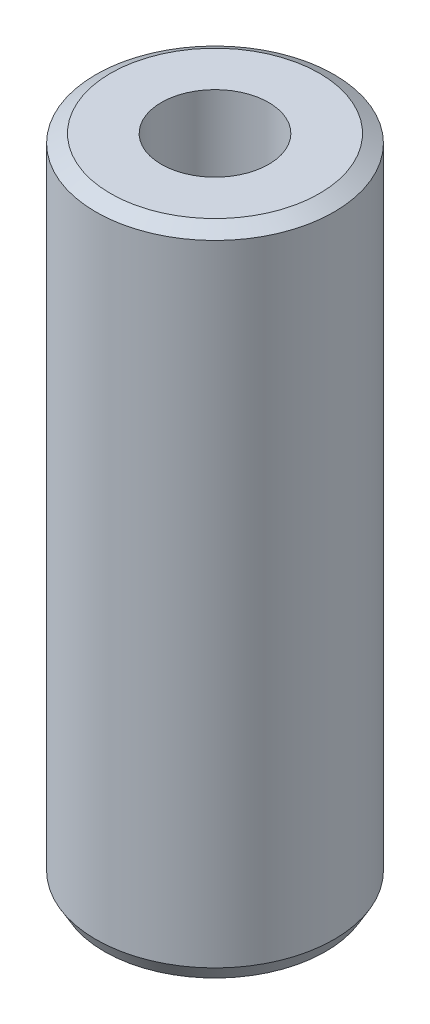
SolidWorks part; units mm, degrees
ref_plane "Front Plane" through (0, 0, 0) normal (0, 0, 1) x (1, 0, 0)
ref_plane "Top Plane" through (0, 0, 0) normal (0, 1, 0) x (1, 0, 0)
ref_plane "Right Plane" through (0, 0, 0) normal (1, 0, 0) x (0, 0, -1)
sketch "Sketch1" plane through (0, 0, 0) normal (0, 1, 0) x (1, 0, 0)
  circle A0 centre (0, 0) radius 47.5
  dimension "SHAFT_OD" = 95
extrude "Boss-Extrude1" add sketch "Sketch1" along normal blind 260.5429
sketch "Sketch2" plane through (0, 0, 0) normal (0, 1, 0) x (1, 0, 0)
  circle A0 centre (0, 0) radius 21.4012
  dimension "BORE_D" = 42.8025
extrude "Cut-Extrude1" cut sketch "Sketch2" along normal through all
chamfer "Chamfer1" distance 3.4004 angle 60 2 edges at (0, 260.5429, 47.5) (0, 0, 47.5) first distance on face at (0, 260.5429, 47.5) first distance on face at (0, 0, 21.4012)
